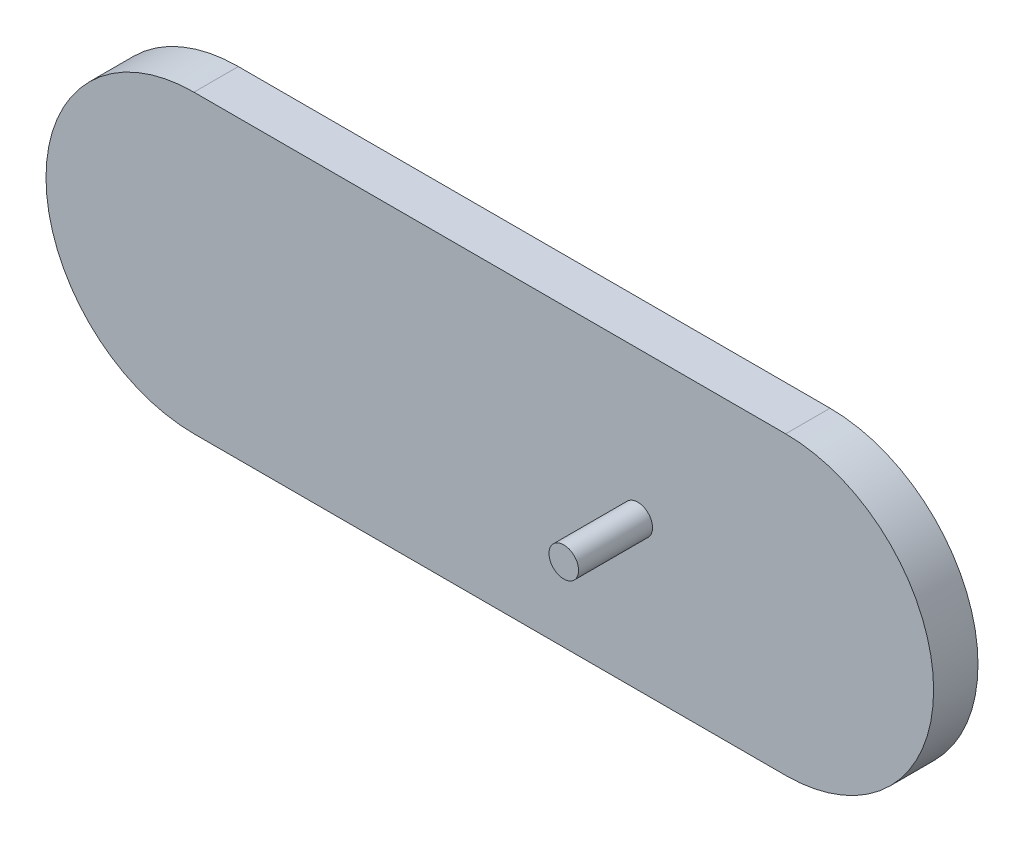
SolidWorks part; units mm, degrees
material "3003 合金"
ref_plane "前视基准面" through (0, 0, 0) normal (0, 0, 1) x (1, 0, 0)
ref_plane "上视基准面" through (0, 0, 0) normal (0, 1, 0) x (1, 0, 0)
ref_plane "右视基准面" through (0, 0, 0) normal (1, 0, 0) x (0, 0, -1)
sketch "草图1" plane through (0, 0, 0) normal (0, 0, 1) x (1, 0, 0)
  line L0 (0, 50) -> (-50, 50)
  line L5 (0, 0) -> (-200, 0)
  line L6 (0, 0) -> (0, 100)
  line L7 (0, 100) -> (-200, 100)
  line L8 (-200, 0) -> (-200, 100)
  circle A6 centre (0, 50) radius 50
  circle A7 centre (0, 50) radius 25
  circle A8 centre (-200, 50) radius 50
  circle A9 centre (-200, 50) radius 25
  circle A10 centre (-50, 50) radius 5
  dimension "D1" = 100
  dimension "D2" = 200
  dimension "D3" = 50
  dimension "D4" = 50
  dimension "D5" = 10
extrude "凸台-拉伸1" add sketch "草图1" along normal blind 15 contours L7 L8 L5 L6
extrude "凸台-拉伸4" add sketch "草图1<10>" along normal blind 15 contours A7 L6 A6 | L6 A7 | L8 A9 | A9 L8 A8 region at (10.6103, 50, 0) region at (1.118, 87.5, 0) region at (-201.118, 87.5, 0) region at (-210.6103, 50, 0)
sketch "草图1<10>" plane through (0, 0, 0) normal (0, 0, 1) x (1, 0, 0) same geometry as "草图1"
extrude "凸台-拉伸6" add sketch "草图1<16>" along normal blind 40 contours A6 A10 L0 | A6 A10 | L0 A10 A6 region at (-47.8335, 47.9132, 0) region at (-47.8335, 52.0868, 0) region at (-52.0764, 50, 0)
sketch "草图1<16>" plane through (0, 0, 0) normal (0, 0, 1) x (1, 0, 0) same geometry as "草图1"
